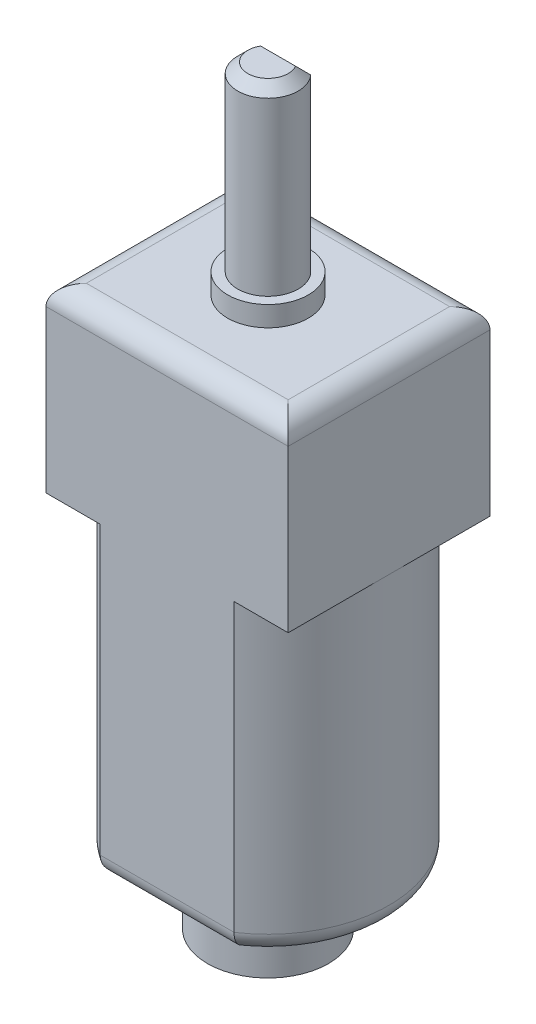
SolidWorks part; units mm, degrees
material "2014 Сплав"
ref_plane "Спереди" through (0, 0, 0) normal (0, 0, 1) x (1, 0, 0)
ref_plane "Сверху" through (0, 0, 0) normal (0, 1, 0) x (1, 0, 0)
ref_plane "Справа" through (0, 0, 0) normal (1, 0, 0) x (0, 0, -1)
sketch "Эскиз3" plane through (0, 0, 0) normal (0, 1, 0) x (1, 0, 0)
  line L1 (-3.3166, -5) -> (3.3166, -5)
  line L3 (-3.3166, 5) -> (3.3166, 5)
  line L5 (-6, -5) -> (6, 5) construction
  line L6 (-6, 5) -> (6, -5) construction
  arc A0 (-3.3166, 5) -> (-3.3166, -5) centre (0, 0) ccw
  arc A1 (3.3166, -5) -> (3.3166, 5) centre (0, 0) ccw
  dimension "D3" = 12
  dimension "D1" = 10
  dimension "D2" = 12
extrude "Бобышка-Вытянуть2" add sketch "Эскиз3" along normal blind 15.2
sketch "Эскиз4" plane through (0, 15.2, 0) normal (0, 1, 0) x (1, 0, 0)
  line L1 (6, 5) -> (-6, 5)
  line L2 (6, 5) -> (6, -5)
  line L3 (6, -5) -> (-6, -5)
  line L4 (-6, 5) -> (-6, -5)
  line L5 (6, 5) -> (-6, -5) construction
  line L6 (6, -5) -> (-6, 5) construction
  point P0 (0, 0)
  dimension "D1" = 12
  dimension "D2" = 10
extrude "Бобышка-Вытянуть3" add sketch "Эскиз4" along normal blind 9
sketch "Эскиз5" plane through (0, 24.2, 0) normal (0, 1, 0) x (1, 0, 0)
  circle A0 centre (0, 0) radius 2
  dimension "D1" = 4
extrude "Бобышка-Вытянуть4" add sketch "Эскиз5" along normal blind 1
sketch "Эскиз6" plane through (0, 25.2, 0) normal (0, 1, 0) x (1, 0, 0)
  circle A0 centre (0, 0) radius 1.5
  dimension "D1" = 3
extrude "Бобышка-Вытянуть5" add sketch "Эскиз6" along normal blind 9
sketch "Эскиз7" plane through (0, 34.2, 0) normal (0, 1, 0) x (1, 0, 0)
  line L0 (-1.118, 1) -> (1.118, 1)
  arc A0 (1.118, 1) -> (-1.118, 1) centre (0, 0) ccw
  dimension "D2" = 3
  dimension "D1" = 1
extrude "Вырез-Вытянуть2" cut sketch "Эскиз7" against normal blind 8
chamfer "Фаска1" distance 0.5 angle 45 2 edges at (0, 34.2, 1.5) (0, 34.2, -1)
fillet "Скругление1" radius 1 8 edges at (0, 0, 5) (6, 0, 0) (0, 0, -5) (-6, 0, 0) (0, 24.2, -5) (-6, 24.2, 0) (0, 24.2, 5) (6, 24.2, 0)
sketch "Эскиз8" plane through (0, 0, 0) normal (0, -1, 0) x (1, 0, 0)
  circle A0 centre (0, 0) radius 3
  dimension "D1" = 6
extrude "Бобышка-Вытянуть6" add sketch "Эскиз8" along normal blind 3
